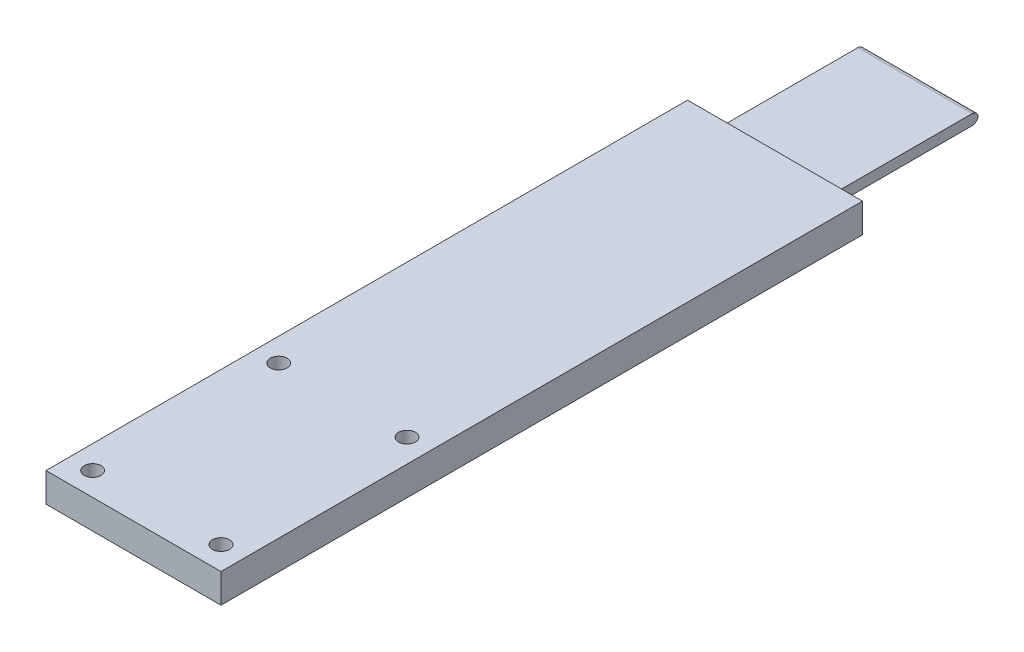
SolidWorks part; units mm, degrees
ref_plane "前视基准面" through (0, 0, 0) normal (0, 0, 1) x (1, 0, 0)
ref_plane "上视基准面" through (0, 0, 0) normal (0, 1, 0) x (1, 0, 0)
ref_plane "右视基准面" through (0, 0, 0) normal (1, 0, 0) x (0, 0, -1)
other "Configuration Table"
sketch "草图1" plane through (0, 0, 0) normal (0, 0, 1) x (1, 0, 0)
  line L1 (0, 0) -> (-30, 0)
  line L2 (0, 0) -> (0, 5)
  line L3 (0, 5) -> (-30, 5)
  line L4 (-30, 0) -> (-30, 5)
  dimension "D1" = 30
  dimension "D2" = 5
extrude "凸台-拉伸1" add sketch "草图1" along normal blind 110
sketch "草图2" plane through (0, 5, 0) normal (0, 1, 0) x (1, 0, 0)
  line L0 (-30, -110) -> (-26, -110) construction
  line L1 (0, -110) -> (-30, -110) construction
  line L2 (-26, -110) -> (-26, -106) construction
  line L3 (-26, -106) -> (-26, -74.1) construction
  line L4 (-15, -110) -> (-15, -30.41) construction
  circle A0 centre (-26, -106) radius 1.45
  circle A1 centre (-26, -74.1) radius 1.45
  circle A2 centre (-4, -106) radius 1.45
  circle A3 centre (-4, -74.1) radius 1.45
  dimension "D4" = 2.9
  dimension "D5" = 2.9
  dimension "D1" = 4
  dimension "D2" = 4
  dimension "D3" = 31.9
extrude "切除-拉伸1" cut sketch "草图2" against normal blind 60
sketch "草图3" plane through (0, 0, 0) normal (0, -1, 0) x (1, 0, 0)
  line L0 (0, 110) -> (0, 0) construction
  line L1 (-30, 0) -> (0, 0)
  line L2 (-30, 0) -> (-30, 10)
  line L3 (-30, 10) -> (0, 10)
  line L4 (0, 0) -> (0, 10)
  dimension "D1" = 10
sketch "草图4" plane through (0, 0, 0) normal (0, 0, -1) x (-1, 0, 0)
  line L0 (30, 5) -> (30, 0) construction
  line L1 (5.2, 3.4) -> (24.8, 3.4)
  line L2 (5.2, 3.4) -> (5.2, 1.6)
  line L3 (5.2, 1.6) -> (24.8, 1.6)
  line L4 (24.8, 3.4) -> (24.8, 1.6)
  line L5 (0, 0) -> (0, 5) construction
  line L6 (0, 5) -> (30, 5) construction
  line L7 (30, 0) -> (0, 0) construction
  dimension "D1" = 5.2
  dimension "D2" = 5.2
  dimension "D3" = 1.6
  dimension "D4" = 1.6
extrude "凸台-拉伸2" add sketch "草图4" along normal blind 25
fillet "圆角1" radius 1 2 edges at (-15, 1.6, -25) (-15, 3.4, -25)
